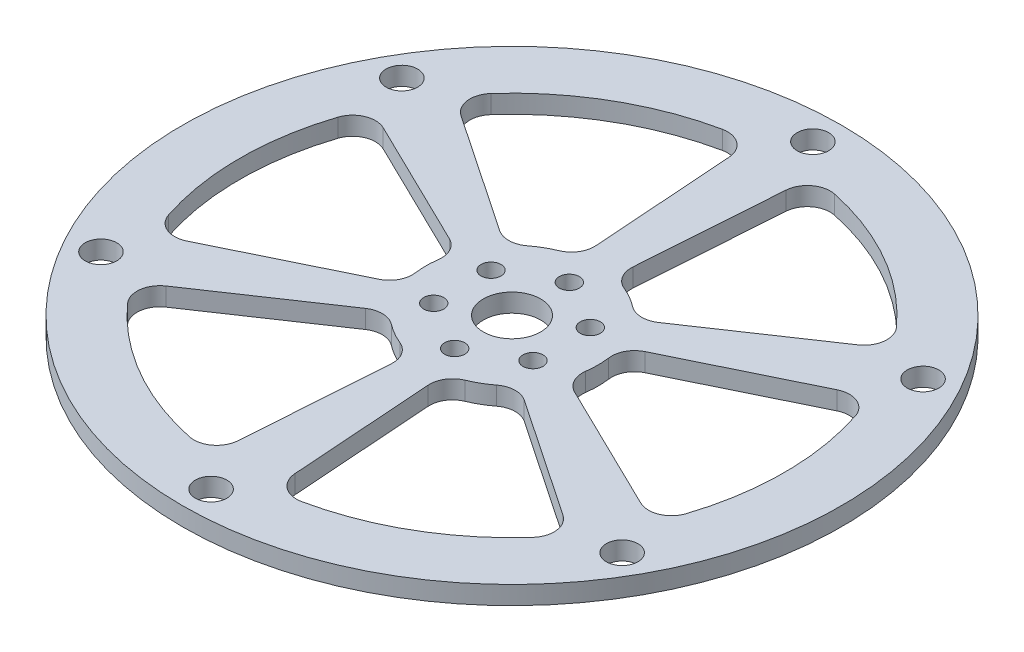
SolidWorks part; units mm, degrees
material "Stainless Steel (ferritic)"
ref_plane "Front Plane" through (0, 0, 0) normal (0, 0, 1) x (1, 0, 0)
ref_plane "Top Plane" through (0, 0, 0) normal (0, 1, 0) x (1, 0, 0)
ref_plane "Right Plane" through (0, 0, 0) normal (1, 0, 0) x (0, 0, -1)
sketch "Sketch1" plane through (0, 0, 0) normal (0, 1, 0) x (1, 0, 0)
  circle A0 centre (0, 0) radius 10 construction
  circle A2 centre (0, 0) radius 15
  circle A3 centre (0, 0) radius 5
  dimension "D1" = 20
  dimension "D3" = 5
extrude "Boss-Extrude1" add sketch "Sketch1" along normal blind 3.2
sketch "Sketch2" plane through (0, 0, 0) normal (0, 1, 0) x (1, 0, 0)
  circle A0 centre (0, 0) radius 52.5 construction
  circle A1 centre (0, 0) radius 47.5
  circle A2 centre (0, 0) radius 57.5
  dimension "D3" = 105
extrude "Boss-Extrude2" add sketch "Sketch2" along normal blind 3.2 separate body
sketch "Sketch5" plane through (0, 0, 0) normal (0, 1, 0) x (1, 0, 0)
  line L0 (0, 96.6167) -> (0, -103.046) construction
  line L1 (-5.2733, 47.2064) -> (-3, 14.6969)
  line L2 (5.2733, 47.2064) -> (3, 14.6969)
  circle A0 centre (0, 0) radius 15 construction
  circle A1 centre (0, 0) radius 47.5 construction
  arc A2 (3, 14.6969) -> (-3, 14.6969) centre (0, 0) ccw
  arc A3 (5.2733, 47.2064) -> (-5.2733, 47.2064) centre (0, 0) ccw
  arc A4 (-5.2733, 47.2064) -> (0, -47.5) centre (0, 0) ccw construction
  arc A5 (-3, 14.6969) -> (0, -15) centre (0, 0) ccw construction
  arc A6 (0, -15) -> (3, 14.6969) centre (0, 0) ccw construction
  arc A7 (0, -47.5) -> (5.2733, 47.2064) centre (0, 0) ccw construction
  dimension "D1" = 3
  dimension "D2" = 3
  dimension "D3" = 4
  dimension "D4" = 4
extrude "Boss-Extrude3" add sketch "Sketch5" along normal blind 3.2
sketch "Sketch3" plane through (0, 0, 0) normal (0, 1, 0) x (1, 0, 0)
  circle A0 centre (0, 10) radius 1.75
  dimension "D1" = 3.5
  dimension "D2" = 10
extrude "Cut-Extrude2" cut sketch "Sketch3" along normal through all
sketch "Sketch4" plane through (0, 0, 0) normal (0, 1, 0) x (1, 0, 0)
  circle A0 centre (0, 52.5) radius 2.75
  dimension "D1" = 5.5
  dimension "D2" = 52.5
extrude "Cut-Extrude3" cut sketch "Sketch4" along normal through all
fillet "Fillet1" radius 4 4 edges at (5.2733, 1.6, -47.2064) (3, 1.6, -14.6969) (-3, 1.6, -14.6969) (-5.2733, 1.6, -47.2064)
pattern_circular "CirPattern1" count 6 over 360 about axis through (0, 3.2, 0) along (0, 1, 0) of "Boss-Extrude3", "Cut-Extrude3", "Fillet1"
pattern_circular "CirPattern2" count 6 over 360 about axis through (0, 3.2, 0) along (0, 1, 0) of "Cut-Extrude2"
equation "\"flywheel_mounting_hole_circle_diameter\"= 105mm"
equation "\"motor_shaft_mounting_hole_circle_diameter\"= 20mm"
equation "\"ring_width\"= 10mm"
equation "\"material_thickness\"= 3.2mm"
equation "\"D1@Sketch1\"=\"motor_shaft_mounting_hole_circle_diameter\""
equation "\"D2@Sketch1\"=\"ring_width\"/2"
equation "\"D3@Sketch1\"=\"ring_width\"/2"
equation "\"D1@Boss-Extrude1\"=\"material_thickness\""
equation "\"D1@Sketch2\"=\"ring_width\"/2"
equation "\"D2@Sketch2\"=\"ring_width\"/2"
equation "\"D3@Sketch2\"=\"flywheel_mounting_hole_circle_diameter\""
equation "\"D1@Boss-Extrude2\"=\"material_thickness\""
equation "\"D2@Sketch3\"=\"motor_shaft_mounting_hole_circle_diameter\"/2"
equation "\"D2@Sketch4\"=\"flywheel_mounting_hole_circle_diameter\"/2"
equation "\"D4@Sketch5\"=\"D3@Sketch5\""
equation "\"D1@Boss-Extrude3\"=\"material_thickness\""
